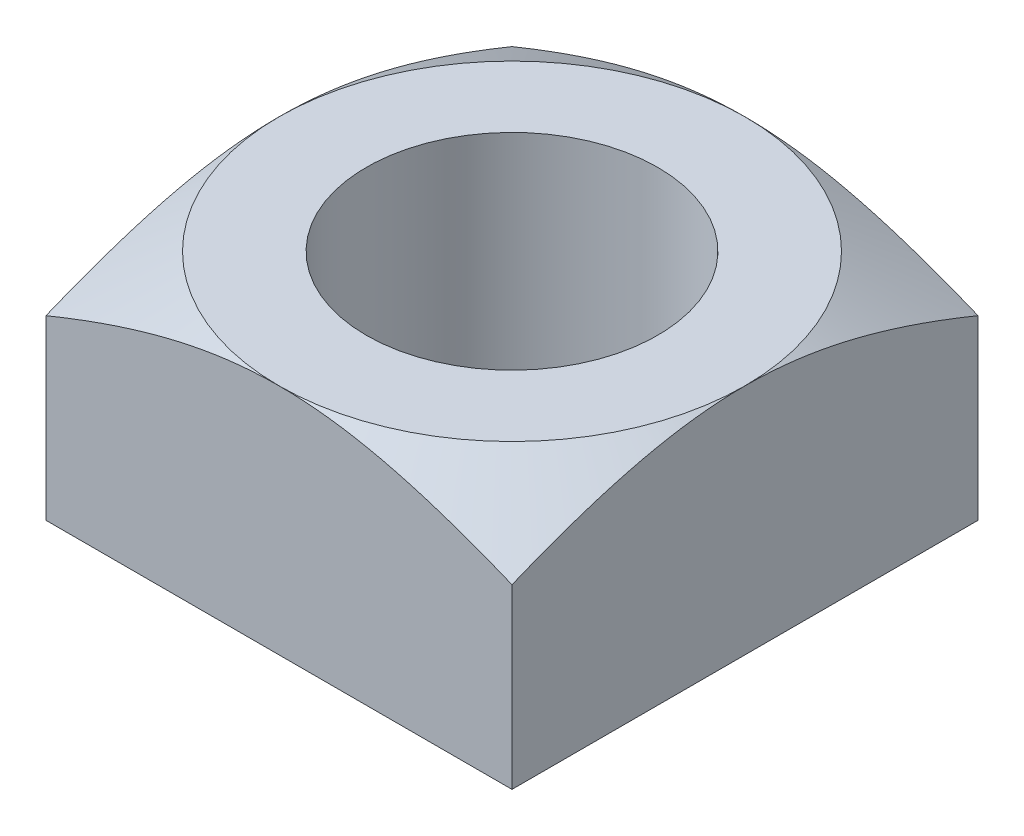
SolidWorks part; units mm, degrees
ref_plane "Front Plane" through (0, 0, 0) normal (0, 0, 1) x (1, 0, 0)
ref_plane "Top Plane" through (0, 0, 0) normal (0, 1, 0) x (1, 0, 0)
ref_plane "Right Plane" through (0, 0, 0) normal (1, 0, 0) x (0, 0, -1)
sketch "Sketch1" plane through (0, 0, 0) normal (0, 1, 0) x (1, 0, 0)
  line L1 (-4, 2.3094) -> (-4, -4.1064) construction
  line L4 (4, -2.3094) -> (4, 4.1064) construction
  line L7 (-4, 4) -> (4, 4)
  line L8 (-4, 4) -> (-4, -4)
  line L9 (-4, -4) -> (4, -4)
  line L10 (4, 4) -> (4, -4)
  line L11 (26.503, -10.6827) -> (20.9468, -7.4748) [skipped]
  line L12 (22.503, 17.6109) -> (16.9468, 14.403) [skipped]
  line L13 (0, -4.6188) -> (5.5562, -1.4109) [skipped]
  line L14 (-4, -2.3094) -> (1.5562, -5.5173) [skipped]
  circle A0 centre (0, 0) radius 4 construction
  circle A1 centre (0, 0) radius 2.5
  dimension "Thread Size" = 5
  dimension "Hex" = 8
extrude "Boss-Extrude1" add sketch "Sketch1" along normal mid plane 4
sketch "Sketch2" plane through (0, 2, 0) normal (0, 1, 0) x (1, 0, 0)
  circle A1 centre (0, 0) radius 2.5
  circle A3 centre (0, 0) radius 2.5 construction
curve "Helix/Spiral1" pitch 0.8 height 4.8 turns 6 parameters "Pitch"=0.8
sketch "Sketch3" plane through (0, 0, 0) normal (1, 0, 0) x (0, 0, -1)
  line L0 (1.9804, 2.4) -> (2.5, 2.7)
  line L1 (2.5, 2.7) -> (2.5, 2)
  line L2 (2.5, 2) -> (1.9804, 2.3)
  line L3 (1.9804, 2.3) -> (1.9804, 2.4)
  line L4 (2.2402, 2.55) -> (2.2402, 2.15) construction
  line L5 (1.9804, 2.35) -> (2.5, 2.35) construction
  line L6 (2.5, 2) -> (-2.5, 2) construction
  dimension "D1" = 60
  dimension "D2" = 0.1
  dimension "D3" = 0.4
sweep "Sweep1" [suppressed] add profiles "Sketch3" path "Helix/Spiral1"
sketch "Sketch4" plane through (0, 2, 0) normal (0, 1, 0) x (1, 0, 0)
  circle A1 centre (0, 0) radius 2.5
  circle A2 centre (0, 0) radius 2.5
  dimension "D1" = 0
extrude "Cut-Extrude1" [suppressed] cut sketch "Sketch4" along normal through all and the other way through all draft 45
sketch "Sketch5" plane through (0, 2, 0) normal (0, 1, 0) x (1, 0, 0)
  circle A1 centre (0, 0) radius 4
  circle A2 centre (0, 0) radius 4 construction
extrude "Cut-Extrude2" cut sketch "Sketch5" against normal through all draft 60 flip side to cut
mirror "Mirror1" [suppressed] about plane through (0, 0, 0) normal (0, 1, 0)
equation "\"D2@Sketch3\" = \"Pitch@Helix/Spiral1\"*.125"
equation "\"D3@Sketch3\" = \"Pitch@Helix/Spiral1\"*.5"
equation "\"D3@Helix/Spiral1\" = \"Height@Boss-Extrude1\"+\"Pitch@Helix/Spiral1\""
